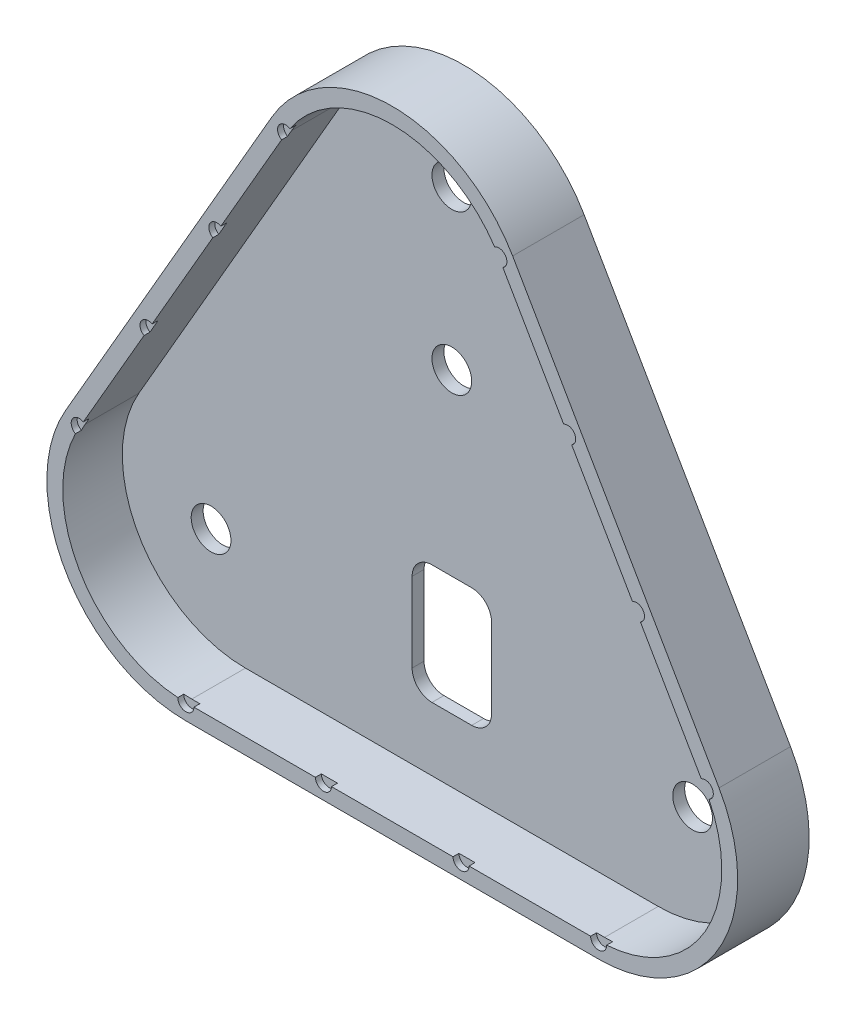
SolidWorks part; units mm, degrees
ref_plane "Plano frontal" through (0, 0, 0) normal (0, 0, 1) x (1, 0, 0)
ref_plane "Plano superior" through (0, 0, 0) normal (0, 1, 0) x (1, 0, 0)
ref_plane "Plano direito" through (0, 0, 0) normal (1, 0, 0) x (0, 0, -1)
sketch "Esboço2" plane through (0, 0, 0) normal (0, 0, 1) x (1, 0, 0)
  line L3 (-30.3109, 77.5) -> (-82.2724, -12.5)
  line L4 (-51.9615, -65) -> (51.9615, -65)
  line L5 (82.2724, -12.5) -> (30.3109, 77.5)
  arc A3 (-82.2724, -12.5) -> (-51.9615, -65) centre (-51.9615, -30) ccw
  arc A4 (51.9615, -65) -> (82.2724, -12.5) centre (51.9615, -30) ccw
  arc A5 (30.3109, 77.5) -> (-30.3109, 77.5) centre (0, 60) ccw
extrude "Ressalto-extrusão1" add sketch "Esboço2" along normal blind 3
sketch "Esboço4" plane through (0, 0, 0) normal (0, 0, 1) x (1, 0, 0)
  line L0 (0, 0) -> (0, 70) construction
  circle A3 centre (0, 70) radius 5
  circle A4 centre (60.6218, -35) radius 5
  circle A5 centre (-60.6218, -35) radius 5
  circle A6 centre (0, 30) radius 5
  point P13 (0, 0)
  dimension "D1" = 70
  dimension "D2" = 10
  dimension "D4" = 10
  dimension "D5" = 30
  dimension "D3" = 3
extrude "Corte-extrusão1" cut sketch "Esboço4" along normal blind 3
sketch "Esboço5" plane through (0, 0, 3) normal (0, 0, 1) x (1, 0, 0)
  line L0 (-51.9615, -65) -> (51.9615, -65) construction
  line L1 (82.2724, -12.5) -> (30.3109, 77.5) construction
  line L2 (-30.3109, 77.5) -> (-82.2724, -12.5) construction
  line L3 (-51.9615, -65) -> (51.9615, -65)
  line L4 (82.2724, -12.5) -> (30.3109, 77.5)
  line L5 (-30.3109, 77.5) -> (-82.2724, -12.5)
  line L6 (-51.9615, -61) -> (51.9615, -61)
  line L7 (78.8083, -14.5) -> (26.8468, 75.5)
  line L8 (-26.8468, 75.5) -> (-78.8083, -14.5)
  arc A0 (-82.2724, -12.5) -> (-51.9615, -65) centre (-51.9615, -30) ccw construction
  arc A1 (51.9615, -65) -> (82.2724, -12.5) centre (51.9615, -30) ccw construction
  arc A2 (30.3109, 77.5) -> (-30.3109, 77.5) centre (0, 60) ccw construction
  arc A3 (-82.2724, -12.5) -> (-51.9615, -65) centre (-51.9615, -30) ccw
  arc A4 (51.9615, -65) -> (82.2724, -12.5) centre (51.9615, -30) ccw
  arc A5 (30.3109, 77.5) -> (-30.3109, 77.5) centre (0, 60) ccw
  arc A6 (51.9615, -61) -> (78.8083, -14.5) centre (51.9615, -30) ccw
  arc A7 (26.8468, 75.5) -> (-26.8468, 75.5) centre (0, 60) ccw
  arc A8 (-78.8083, -14.5) -> (-51.9615, -61) centre (-51.9615, -30) ccw
  dimension "D1" = 4
extrude "Ressalto-extrusão2" add sketch "Esboço5" along normal blind 15
sketch "Esboço6" plane through (0, 0, 3) normal (0, 0, 1) x (1, 0, 0)
  line L0 (0, -65) -> (0, -30) construction
  line L1 (-51.9615, -65) -> (51.9615, -65) construction
  line L3 (-10, -45) -> (10, -45)
  line L4 (-10, -45) -> (-10, -15)
  line L5 (-10, -15) -> (10, -15)
  line L6 (10, -45) -> (10, -15)
  line L7 (-10, -45) -> (10, -15) construction
  line L8 (-10, -15) -> (10, -45) construction
  dimension "D1" = 35
  dimension "D2" = 20
  dimension "D3" = 30
extrude "Corte-extrusão2" cut sketch "Esboço6" against normal up to surface (3 mm away) up to face at (5, 70, 0)
fillet "Filete1" radius 5 4 edges at (-10, -45, 1.5) (10, -45, 1.5) (10, -15, 1.5) (-10, -15, 1.5)
sketch "Esboço7" plane through (0, 0, 18) normal (0, 0, 1) x (1, 0, 0)
  circle A0 centre (-26.8468, 75.5) radius 2.025
  circle A1 centre (26.8468, 75.5) radius 2.025
  circle A2 centre (-51.9615, -61) radius 2.025
  circle A3 centre (-44.1668, 45.5009) radius 2.025
  circle A4 centre (-61.4868, 15.5018) radius 2.025
  circle A5 centre (-78.8068, -14.4974) radius 2.025
  circle A6 centre (44.1668, 45.5009) radius 2.025
  circle A7 centre (61.4868, 15.5018) radius 2.025
  circle A8 centre (78.8068, -14.4974) radius 2.025
  circle A9 centre (-17.3215, -61) radius 2.025
  circle A10 centre (17.3185, -61) radius 2.025
  circle A11 centre (51.9585, -61) radius 2.025
  dimension "D4" = 4.05
  dimension "D1" = 4
  dimension "D2" = 4
  dimension "D3" = 4
extrude "Corte-extrusão3" cut sketch "Esboço7" against normal blind 1.5
